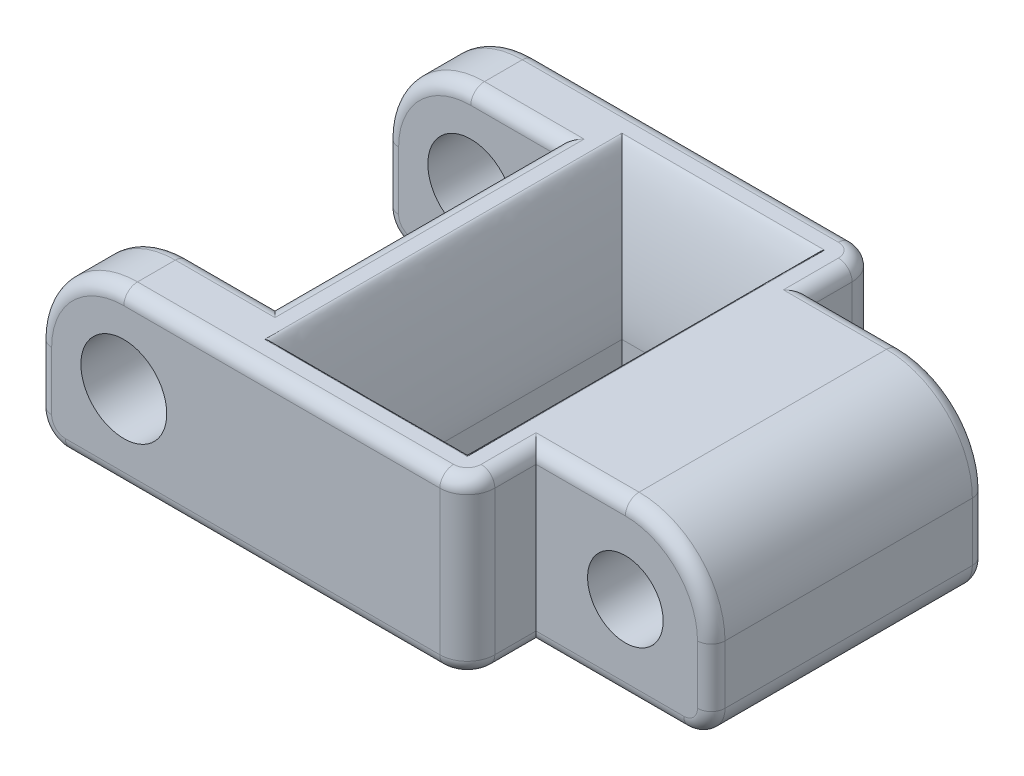
SolidWorks part; units mm, degrees
ref_plane "Front Plane" through (0, 0, 0) normal (0, 0, 1) x (1, 0, 0)
ref_plane "Top Plane" through (0, 0, 0) normal (0, 1, 0) x (1, 0, 0)
ref_plane "Right Plane" through (0, 0, 0) normal (1, 0, 0) x (0, 0, -1)
sketch "Sketch1" plane through (0, 0, 0) normal (0, 1, 0) x (1, 0, 0)
  line L0 (0, -10.1) -> (0, -12)
  line L1 (0, 0) -> (12.5, 0)
  line L2 (0, 0) -> (0, -1.9)
  line L3 (0, -12) -> (12.5, -12)
  line L4 (12.5, 0) -> (12.5, -2)
  line L5 (12.5, -2) -> (17.6, -2)
  line L7 (12.5, -10) -> (17.6, -10)
  line L8 (17.6, -2) -> (17.6, -10)
  line L9 (0, -1.9) -> (5, -1.9)
  line L11 (0, -10.1) -> (5, -10.1)
  line L12 (5, -1.9) -> (5, -10.1)
  line L13 (12.5, -10) -> (12.5, -12)
  dimension "D1" = 12
  dimension "D2" = 8
  dimension "D3" = 2
  dimension "D4" = 12.5
  dimension "D5" = 5.1
  dimension "D6" = 8.2
  dimension "D7" = 1.9
  dimension "D8" = 5
extrude "Boss-Extrude1" add sketch "Sketch1" along normal blind 5
sketch "Sketch2" plane through (0, 0, 10) normal (0, 0, 1) x (1, 0, 0)
  line L0 (12.5, 5) -> (17.6, 5) construction
  line L1 (17.6, 5) -> (17.6, 0) construction
  line L2 (0, 5) -> (0, 0) construction
  line L3 (0, 5) -> (12.5, 5) construction
  circle A0 centre (15.1, 2.5) radius 1.1
  circle A1 centre (2.5, 2.5) radius 1.25
  dimension "D1" = 2.2
  dimension "D4" = 2.5
  dimension "D2" = 2.5
  dimension "D3" = 2.5
  dimension "D5" = 2.5
  dimension "D6" = 2.5
extrude "Cut-Extrude1" cut sketch "Sketch2" against normal through all both and the other way through all
sketch "Sketch3" plane through (0, 5, 0) normal (0, 1, 0) x (1, 0, 0)
  line L0 (12.5, 0) -> (0, 0) construction
  line L1 (7, -2) -> (10.5, -2)
  line L2 (7, -2) -> (7, -10)
  line L3 (7, -10) -> (10.5, -10)
  line L4 (10.5, -2) -> (10.5, -10)
  line L5 (0, -12) -> (12.5, -12) construction
  line L6 (12.5, -2) -> (12.5, 0) construction
  line L7 (5, -1.9) -> (5, -10.1) construction
  dimension "D1" = 2
  dimension "D2" = 2
  dimension "D3" = 2
  dimension "D4" = 2
  dimension "D5" = 3.5
extrude "Cut-Extrude2" cut sketch "Sketch3" against normal through all
fillet "Fillet1" radius 2.5 3 edges at (0, 5, 0.95) (0, 5, 11.05) (17.6, 5, 6)
fillet "Fillet2" radius 1.2 4 edges at (8.75, 5, 10) (10.5, 5, 6) (8.75, 5, 2) (7, 5, 6) second distance 4 conic rho 0.2 first distance on face at (8.75, 5, 6)
fillet "Fillet3" radius 0.8 5 edges at (0, 0, 0.95) (0, 0, 11.05) (17.6, 0, 6) (12.5, 2.5, 0) (12.5, 2.5, 12)
fillet "Fillet4" radius 0.4 39 edges at (14.65, 0, 2) (17.3657, 0.2343, 2) (17.6, 1.65, 2) (16.8678, 4.2678, 2) (14.65, 0, 10) (17.3657, 0.2343, 10) (17.6, 1.65, 10) (16.8678, 4.2678, 10) (12.5, 0, 10.6) (12.2657, 0, 11.7657) (6.25, 0, 12) (0.2343, 0.2343, 12) (0, 1.65, 12) (0.7322, 4.2678, 12) (2.9, 0, 10.1) (0.2343, 0.2343, 10.1) (0, 1.65, 10.1) (0.7322, 4.2678, 10.1) (2.9, 0, 1.9) (0.2343, 0.2343, 1.9) (0, 1.65, 1.9) (0.7322, 4.2678, 1.9) (12.5, 0, 1.4) (12.2657, 0, 0.2343) (6.25, 0, 0) (0.2343, 0.2343, 0) (0, 1.65, 0) (0.7322, 4.2678, 0) (13.8, 5, 2) (13.8, 5, 10) (12.5, 5, 10.6) (12.2657, 5, 11.7657) (7.1, 5, 12) (3.75, 5, 10.1) (5, 5, 6) (3.75, 5, 1.9) (7.1, 5, 0) (12.2657, 5, 0.2343) (12.5, 5, 1.4)
equation "\"D3@Sketch1\"=\"D1@Sketch1\"/2-\"D2@Sketch1\"/2"
equation "\"D6@Sketch1\"=8.2"
equation "\"D7@Sketch1\"=\"D1@Sketch1\"/2-\"D6@Sketch1\"/2"
equation "\"D2@Sketch2\"=\"D1@Boss-Extrude1\"/2"
equation "\"D3@Sketch2\"=\"D2@Sketch2\""
equation "\"D4@Sketch2\"=\"D2@Sketch2\""
equation "\"D5@Sketch2\"=\"D3@Sketch2\""
equation "\"D6@Sketch2\"=\"D2@Sketch2\""
